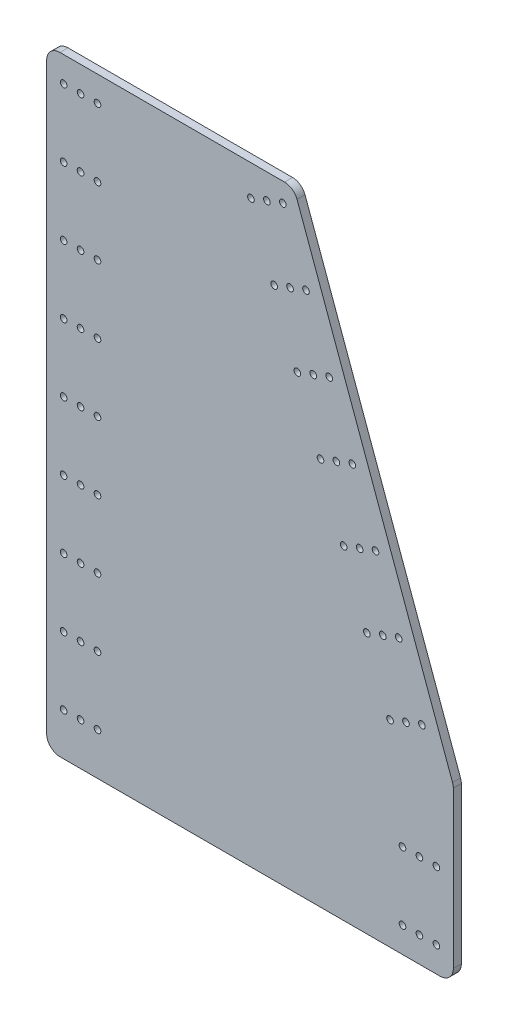
SolidWorks part; units mm, degrees
ref_plane "Front Plane" through (0, 0, 0) normal (0, 0, 1) x (1, 0, 0)
ref_plane "Top Plane" through (0, 0, 0) normal (0, 1, 0) x (1, 0, 0)
ref_plane "Right Plane" through (0, 0, 0) normal (1, 0, 0) x (0, 0, -1)
sketch "Sketch1" plane through (0, 0, 0) normal (0, 0, 1) x (1, 0, 0)
  line L1 (268.47, 228.6) -> (185.2664, 457.2)
  line L2 (185.2664, 457.2) -> (0, 457.2)
  line L3 (268.47, 228.6) -> (304.8, 128.7843)
  line L4 (304.8, 128.7843) -> (304.8, 0)
  line L6 (304.8, 0) -> (0, 0)
  line L7 (0, 0) -> (0, 457.2)
  dimension "D3" = 128.7843
  dimension "D24" = 106.2217
  dimension "D4" = 457.2
extrude "Boss-Extrude1" add sketch "Sketch1" along normal blind 6 contours L3 L4 L6 L7 L2 L1
fillet "Fillet1" radius 10 5 edges at (304.8, 0, 3) (304.8, 128.7843, 3) (0, 0, 3) (185.2664, 457.2, 3) (0, 457.2, 3)
sketch "Sketch2" plane through (0, 0, 6) normal (0, 0, 1) x (1, 0, 0)
  line L0 (0, 10) -> (0, 447.2) construction
  line L1 (178.2644, 457.2) -> (10, 457.2) construction
  line L2 (304.8, 127.021) -> (304.8, 10) construction
  line L3 (294.8, 0) -> (10, 0) construction
  line L4 (12.7, 438.15) -> (12.7, 387.35) construction
  line L5 (153.1176, 434.1313) -> (165.0517, 438.475) construction
  line L6 (165.0517, 438.475) -> (176.9858, 442.8186) construction
  line L7 (304.1969, 130.4412) -> (187.6613, 450.6202) construction
  line L8 (266.7, 19.05) -> (266.7, 69.85) construction
  line L9 (153.1176, 434.1313) -> (170.4922, 386.3949) construction
  circle A0 centre (12.7, 438.15) radius 2.4892
  circle A1 centre (25.4, 438.15) radius 2.4892
  circle A2 centre (38.1, 438.15) radius 2.4892
  circle A3 centre (266.7, 19.05) radius 2.4892
  circle A4 centre (279.4, 19.05) radius 2.4892
  circle A5 centre (292.1, 19.05) radius 2.4892
  circle A6 centre (12.7, 387.35) radius 2.4892
  circle A7 centre (25.4, 387.35) radius 2.4892
  circle A8 centre (38.1, 387.35) radius 2.4892
  circle A9 centre (12.7, 336.55) radius 2.4892
  circle A10 centre (25.4, 336.55) radius 2.4892
  circle A11 centre (38.1, 336.55) radius 2.4892
  circle A12 centre (12.7, 285.75) radius 2.4892
  circle A13 centre (25.4, 285.75) radius 2.4892
  circle A14 centre (38.1, 285.75) radius 2.4892
  circle A15 centre (12.7, 234.95) radius 2.4892
  circle A16 centre (25.4, 234.95) radius 2.4892
  circle A17 centre (38.1, 234.95) radius 2.4892
  circle A18 centre (12.7, 184.15) radius 2.4892
  circle A19 centre (25.4, 184.15) radius 2.4892
  circle A20 centre (38.1, 184.15) radius 2.4892
  circle A21 centre (12.7, 133.35) radius 2.4892
  circle A22 centre (25.4, 133.35) radius 2.4892
  circle A23 centre (38.1, 133.35) radius 2.4892
  circle A24 centre (12.7, 82.55) radius 2.4892
  circle A25 centre (25.4, 82.55) radius 2.4892
  circle A26 centre (38.1, 82.55) radius 2.4892
  circle A27 centre (12.7, 31.75) radius 2.4892
  circle A28 centre (25.4, 31.75) radius 2.4892
  circle A29 centre (38.1, 31.75) radius 2.4892
  circle A57 centre (176.9858, 442.8186) radius 2.4892
  circle A58 centre (165.0517, 438.475) radius 2.4892
  circle A59 centre (153.1176, 434.1313) radius 2.4892
  circle A60 centre (266.7, 69.85) radius 2.4892
  circle A61 centre (279.4, 69.85) radius 2.4892
  circle A62 centre (292.1, 69.85) radius 2.4892
  circle A72 centre (170.4922, 386.3949) radius 2.4892
  circle A73 centre (182.4263, 390.7386) radius 2.4892
  circle A74 centre (194.3604, 395.0822) radius 2.4892
  circle A75 centre (187.8668, 338.6585) radius 2.4892
  circle A76 centre (199.8009, 343.0022) radius 2.4892
  circle A77 centre (211.735, 347.3459) radius 2.4892
  circle A78 centre (205.2415, 290.9222) radius 2.4892
  circle A79 centre (217.1756, 295.2658) radius 2.4892
  circle A80 centre (229.1096, 299.6095) radius 2.4892
  circle A81 centre (222.6161, 243.1858) radius 2.4892
  circle A82 centre (234.5502, 247.5294) radius 2.4892
  circle A83 centre (246.4843, 251.8731) radius 2.4892
  circle A84 centre (239.9907, 195.4494) radius 2.4892
  circle A85 centre (251.9248, 199.793) radius 2.4892
  circle A86 centre (263.8589, 204.1367) radius 2.4892
  circle A87 centre (257.3653, 147.713) radius 2.4892
  circle A88 centre (269.2994, 152.0567) radius 2.4892
  circle A89 centre (281.2335, 156.4003) radius 2.4892
  dimension "D1" = 4.9784
  dimension "D2" = 12.7
  dimension "D3" = 12.7
  dimension "D4" = 12.7
  dimension "D5" = 19.05
  dimension "D6" = 4.9784
  dimension "D7" = 12.7
  dimension "D8" = 12.7
  dimension "D9" = 12.7
  dimension "D10" = 19.05
  dimension "D13" = 12.7
  dimension "D14" = 12.7
  dimension "D15" = 12.7
  dimension "D16" = 4.9784
  dimension "D19" = 14.3814
  dimension "D12" = 50.8
  dimension "D18" = 50.8
  dimension "D21" = 50.8
  dimension "D11" = 9
  dimension "D17" = 2
  dimension "D20" = 7
extrude "Cut-Extrude1" cut sketch "Sketch2" against normal through all
sketch "Sketch3" plane through (0, 0, 0) normal (0, 0, -1) x (-1, 0, 0)
  line L0 (-1344.4273, 0) -> (48655.5727, 0) construction
  line L1 (-304.8, -1002.2603) -> (-304.8, 48997.7397) construction
  line L2 (-294.8, 0) -> (-10, 0) construction
  line L3 (-304.8, 127.021) -> (-304.8, 10) construction
  point P3 (-304.8, 0)
